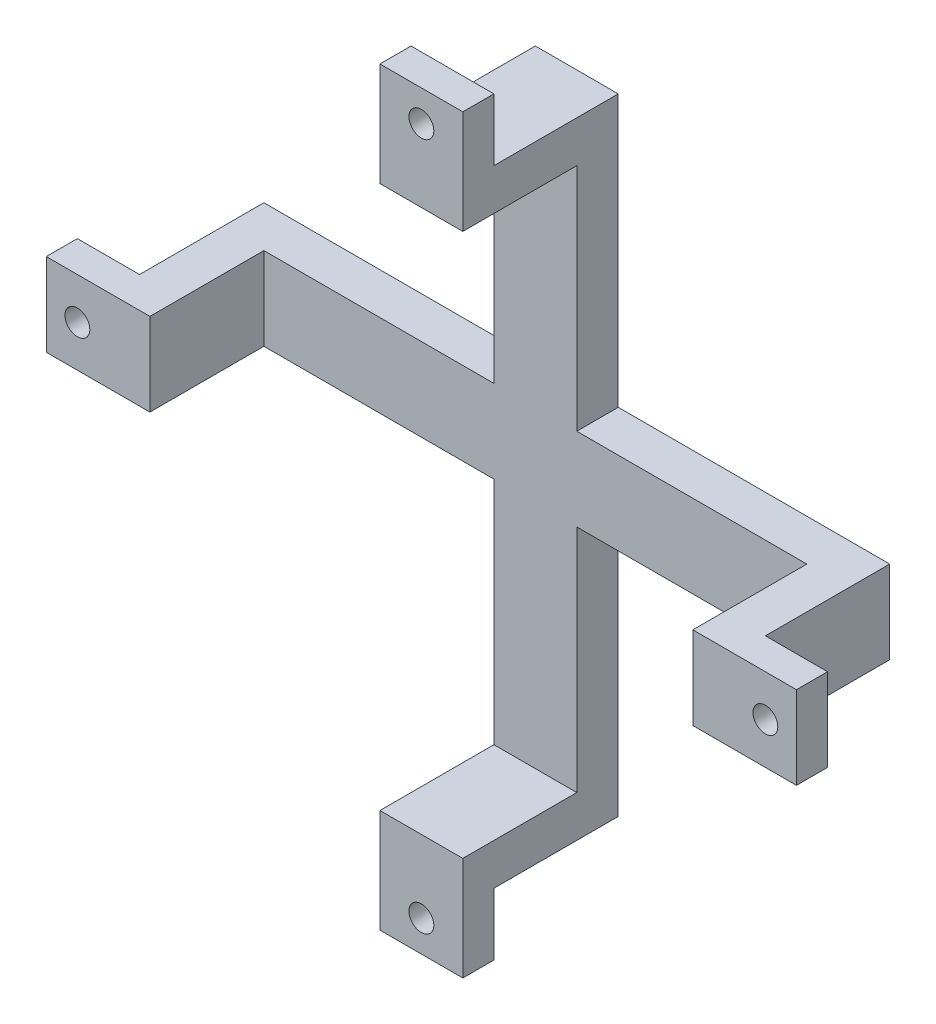
SolidWorks part; units mm, degrees
ref_plane "前视基准面" through (0, 0, 0) normal (0, 0, 1) x (1, 0, 0)
ref_plane "上视基准面" through (0, 0, 0) normal (0, 1, 0) x (1, 0, 0)
ref_plane "右视基准面" through (0, 0, 0) normal (1, 0, 0) x (0, 0, -1)
other "Configuration Table"
sketch "草图1" plane through (0, 0, 0) normal (0, 0, 1) x (1, 0, 0)
  line L1 (-13.1, 2) -> (13.1, 2)
  line L2 (-13.1, 2) -> (-13.1, -2)
  line L3 (-13.1, -2) -> (13.1, -2)
  line L4 (13.1, 2) -> (13.1, -2)
  line L5 (-2, 13.1) -> (2, 13.1)
  line L6 (-2, 13.1) -> (-2, -13.1)
  line L7 (-2, -13.1) -> (2, -13.1)
  line L8 (2, 13.1) -> (2, -13.1)
  line L9 (-2, 13.1) -> (2, 13.1)
  line L10 (-2, 13.1) -> (-2, 15.1)
  line L11 (-2, 15.1) -> (2, 15.1)
  line L12 (2, 13.1) -> (2, 15.1)
  line L13 (13.1, 2) -> (15.1, 2)
  line L14 (13.1, 2) -> (13.1, -2)
  line L15 (13.1, -2) -> (15.1, -2)
  line L16 (15.1, 2) -> (15.1, -2)
  line L17 (2, -13.1) -> (-2, -13.1)
  line L18 (2, -13.1) -> (2, -15.1)
  line L19 (2, -15.1) -> (-2, -15.1)
  line L20 (-2, -13.1) -> (-2, -15.1)
  line L21 (-13.1, -2) -> (-15.1, -2)
  line L22 (-13.1, -2) -> (-13.1, 2)
  line L23 (-13.1, 2) -> (-15.1, 2)
  line L24 (-15.1, -2) -> (-15.1, 2)
  line L25 (-2, 15.1) -> (2, 15.1)
  line L26 (-2, 15.1) -> (-2, 18.1)
  line L27 (-2, 18.1) -> (2, 18.1)
  line L28 (2, 15.1) -> (2, 18.1)
  line L29 (15.1, 2) -> (18.1, 2)
  line L30 (15.1, 2) -> (15.1, -2)
  line L31 (15.1, -2) -> (18.1, -2)
  line L32 (18.1, 2) -> (18.1, -2)
  line L33 (2, -15.1) -> (-2, -15.1)
  line L34 (2, -15.1) -> (2, -18.1)
  line L35 (2, -18.1) -> (-2, -18.1)
  line L36 (-2, -15.1) -> (-2, -18.1)
  line L37 (-15.1, -2) -> (-18.1, -2)
  line L38 (-15.1, -2) -> (-15.1, 2)
  line L39 (-15.1, 2) -> (-18.1, 2)
  line L40 (-18.1, -2) -> (-18.1, 2)
  circle A3 centre (-16.6, 0) radius 0.6
  circle A4 centre (16.6, 0) radius 0.6
  circle A5 centre (0, -16.6) radius 0.6
  circle A6 centre (0, 16.6) radius 0.6
  point P4 (-2, 0)
  point P6 (13.1, 0)
  point P7 (0, 2)
  point P12 (0, -13.1)
  point P41 (-16.6, 2)
  point P43 (16.6, 2)
  point P45 (-2, 16.6)
  point P47 (-2, -16.6)
  dimension "D4" = 3
  dimension "D1" = 4
  dimension "D2" = 26.2
  dimension "D5" = 1.2
  dimension "D3" = 2
extrude "凸台-拉伸1" add sketch "草图1" along normal blind 2 contours L3 L4 L1 L2 | L7 L8 L5 L6
extrude "凸台-拉伸2" add sketch "草图1<6>" along normal blind 7.5 contours L16 L13 L4 L15 | L5 L12 L11 L10 | L7 L20 L19 L18 | L24 L21 L2 L23 region at (-14.1, 0, 0) region at (0, 14.1, 0) region at (14.1, 0, 0) region at (0, -14.1, 0)
sketch "草图1<6>" plane through (0, 0, 0) normal (0, 0, 1) x (1, 0, 0) same geometry as "草图1"
extrude "凸台-拉伸3" add sketch "草图1<7>" against normal blind 1.5 from surface contours L40 L37 L24 L39 | L19 L36 L35 L34 | L32 L29 L16 L31 | L11 L28 L27 L26 region at (-15.15, 0, 0) region at (-1.95, 16.6, 0) region at (16.6, 1.95, 0) region at (0, -15.15, 0) starting at face at (-14.1, 0, 7.5)
sketch "草图1<7>" plane through (0, 0, 0) normal (0, 0, 1) x (1, 0, 0) same geometry as "草图1"
